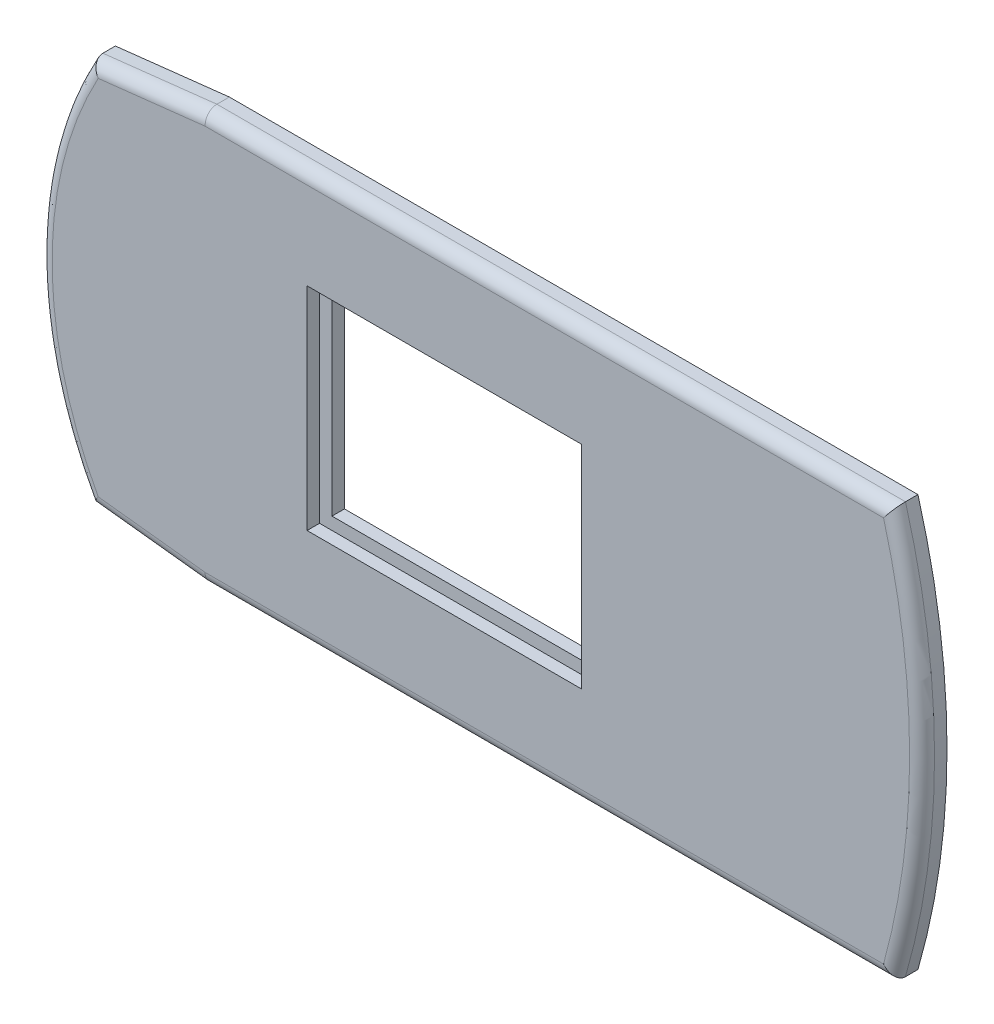
SolidWorks part; units mm, degrees
ref_plane "Plan de face" through (0, 0, 0) normal (0, 0, 1) x (1, 0, 0)
ref_plane "Plan de dessus" through (0, 0, 0) normal (0, 1, 0) x (1, 0, 0)
ref_plane "Plan de droite" through (0, 0, 0) normal (1, 0, 0) x (0, 0, -1)
sketch "Esquisse1" plane through (0, 0, 0) normal (0, 0, 1) x (1, 0, 0)
  line L0 (-192.776, 38.345) -> (-152.776, 42.845)
  line L1 (-152.776, 42.845) -> (115.224, 42.845)
  line L2 (-152.776, 42.845) -> (-152.776, -102.155)
  line L3 (-152.776, -102.155) -> (115.224, -102.155)
  line L4 (115.224, 42.845) -> (115.224, -102.155)
  line L5 (-152.776, 42.845) -> (-192.776, 42.845)
  line L6 (-152.776, 53.8314) -> (-152.776, -102.155)
  line L7 (-152.776, 42.845) -> (-152.776, -102.155)
  line L8 (-152.776, -102.155) -> (-192.776, -102.155)
  line L9 (-192.776, 42.845) -> (-192.776, -102.155)
  line L10 (-152.776, 42.845) -> (-192.776, 42.845)
  line L11 (-152.776, 42.845) -> (-152.776, 38.345)
  line L12 (-152.776, 38.345) -> (-192.776, 38.345)
  line L13 (-192.776, 42.845) -> (-192.776, 38.345)
  line L14 (-152.776, -102.155) -> (-192.776, -102.155)
  line L15 (-152.776, -102.155) -> (-152.776, -97.655)
  line L16 (-152.776, -97.655) -> (-192.776, -97.655)
  line L17 (-192.776, -102.155) -> (-192.776, -97.655)
  line L18 (-192.776, -97.655) -> (-152.776, -102.155)
  line L20 (-107.1692, -67.155) -> (-7.1692, -67.155)
  line L21 (-107.1692, -67.155) -> (-107.1692, 12.845)
  line L22 (-107.1692, 12.845) -> (-7.1692, 12.845)
  line L23 (-7.1692, -67.155) -> (-7.1692, 12.845)
  line L24 (-144.9874, 42.845) -> (-124.9874, 42.845)
  line L25 (-144.9874, 42.845) -> (-144.9874, 40.845)
  line L26 (-144.9874, 40.845) -> (-124.9874, 40.845)
  line L27 (-124.9874, 42.845) -> (-124.9874, 40.845)
  line L28 (-144.9874, -102.155) -> (-124.9874, -102.155)
  line L29 (-144.9874, -102.155) -> (-144.9874, -100.155)
  line L30 (-144.9874, -100.155) -> (-124.9874, -100.155)
  line L31 (-124.9874, -102.155) -> (-124.9874, -100.155)
  line L32 (-112.1692, -72.155) -> (-2.1692, -72.155)
  line L33 (-112.1692, -72.155) -> (-112.1692, 12.845)
  line L34 (-112.1692, 12.845) -> (-2.1692, 12.845)
  line L35 (-2.1692, -72.155) -> (-2.1692, 12.845)
  arc A0 (115.224, -102.155) -> (115.224, 42.845) centre (-162.8429, -29.655) ccw
  arc A1 (-192.776, -97.655) -> (-192.776, 38.345) centre (-62.3678, -29.655) cw
  circle A2 centre (-215.776, -32.155) radius 2.5
  circle A3 centre (130.224, -32.155) radius 2.5
  circle A4 centre (-33.549, -107.155) radius 2.5
  circle A5 centre (-33.549, 47.845) radius 2.5
  point P11 (-210.776, -32.155)
  point P12 (125.224, -32.155)
  point P35 (-57.1692, 12.845)
  dimension "D10" = 30
  dimension "D19" = 5
  dimension "D1" = 268
  dimension "D2" = 145
  dimension "D3" = 40
  dimension "D4" = 4.5
  dimension "D5" = 4.5
  dimension "D6" = 18
  dimension "D7" = 75
  dimension "D8" = 10
  dimension "D9" = 75
  dimension "D11" = 80
  dimension "D12" = 35
  dimension "D13" = 48
  dimension "D14" = 2
  dimension "D15" = 20
  dimension "D16" = 20
  dimension "D17" = 2
  dimension "D18" = 48
  dimension "D20" = 30
  dimension "D21" = 5
  dimension "D22" = 5
  dimension "D23" = 5
  dimension "D24" = 30
  dimension "D25" = 100
  dimension "D26" = 5
  dimension "D27" = 5
extrude "Extru.-Mince1" add sketch "Esquisse1" along normal blind 10 thin contours L3 A0 L1 L0 A1 L18 thin type one direction wall 10
extrude "Boss.-Extru.3" add sketch "Esquisse1<25>" along normal blind 10 contours L31 L3 L4 L1 L27 L26 L25 L2 L7 L29 L30 | L16 L7 L12 L9 | A1 L9 | L4 A0 | L12 L2 L0 | L27 L1 L25 L26 | L16 L18 L2 | L30 L31 L28 L29 region at (-172.776, -29.655, 0) region at (-166.1093, 39.845, 0) region at (-199.4751, -29.655, 0) region at (-148.8817, 39.7979, 0) region at (-166.1093, -99.155, 0) region at (-134.9874, 41.845, 0) region at (118.9476, -29.655, 0)
sketch "Esquisse1<25>" plane through (0, 0, 0) normal (0, 0, 1) x (1, 0, 0) same geometry as "Esquisse1"
extrude "Enlèv. mat.-Extru.1" cut sketch "Esquisse1<26>" along normal blind 5 contours A3 region at (130.224, -32.155, 0)
sketch "Esquisse1<26>" plane through (0, 0, 0) normal (0, 0, 1) x (1, 0, 0) same geometry as "Esquisse1"
extrude "Enlèv. mat.-Extru.2" cut sketch "Esquisse1<27>" along normal blind 5 contours A4
sketch "Esquisse1<27>" plane through (0, 0, 0) normal (0, 0, 1) x (1, 0, 0) same geometry as "Esquisse1"
extrude "Enlèv. mat.-Extru.3" cut sketch "Esquisse1<28>" along normal blind 5 contours A5 region at (-33.549, 47.845, 0)
sketch "Esquisse1<28>" plane through (0, 0, 0) normal (0, 0, 1) x (1, 0, 0) same geometry as "Esquisse1"
extrude "Enlèv. mat.-Extru.4" cut sketch "Esquisse1<29>" along normal blind 5 contours A2 region at (-215.776, -32.155, 0)
sketch "Esquisse1<29>" plane through (0, 0, 0) normal (0, 0, 1) x (1, 0, 0) same geometry as "Esquisse1"
fillet "Congé5" radius 5 6 edges at (-219.4402, -29.655, 10) (-176.2042, 50.2724, 10) (-15.2451, 52.845, 10) (134.52, -29.655, 10) (-15.2451, -112.155, 10) (-176.2042, -109.5824, 10)
extrude "Boss.-Extru.4" add sketch "Esquisse1<30>" along normal blind 5 contours L32 L35 L34 L33 L23 L20 L21 L22 region at (-57.1692, -68.5452, 0)
sketch "Esquisse1<30>" plane through (0, 0, 0) normal (0, 0, 1) x (1, 0, 0) same geometry as "Esquisse1"
